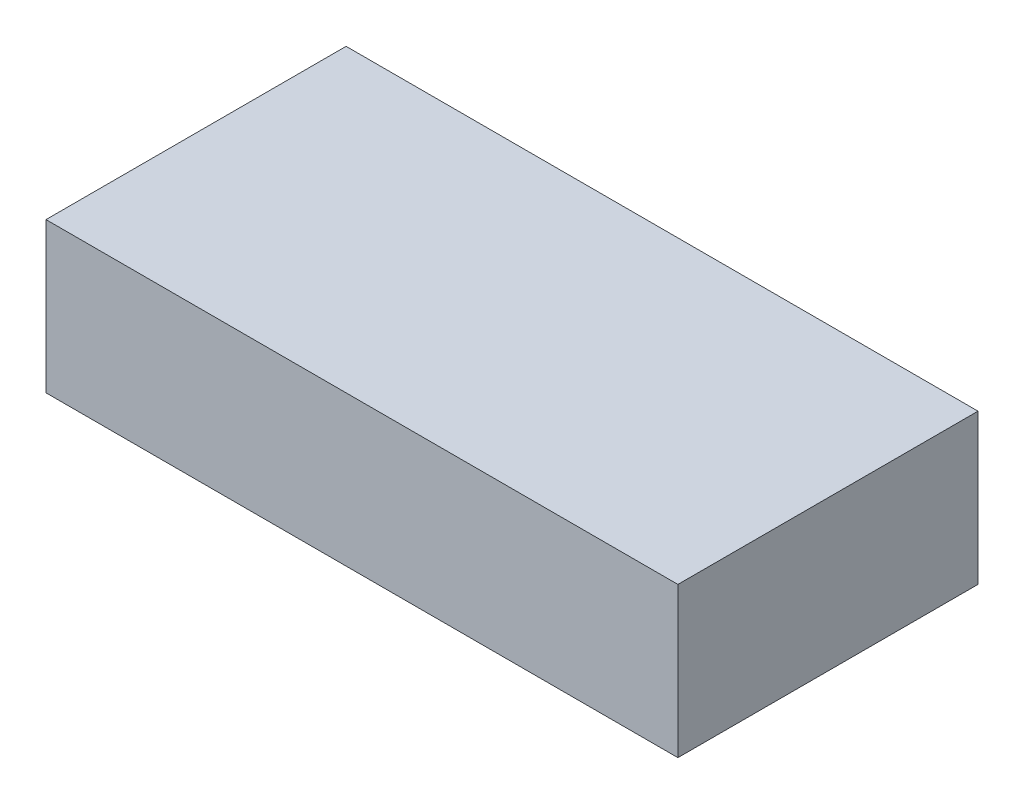
SolidWorks part; units mm, degrees
ref_plane "Front Plane" through (0, 0, 0) normal (0, 0, 1) x (1, 0, 0)
ref_plane "Top Plane" through (0, 0, 0) normal (0, 1, 0) x (1, 0, 0)
ref_plane "Right Plane" through (0, 0, 0) normal (1, 0, 0) x (0, 0, -1)
sketch "Sketch1" plane through (0, 0, 0) normal (0, 1, 0) x (1, 0, 0)
  line L1 (-37.973, -18.034) -> (37.973, -18.034)
  line L2 (-37.973, -18.034) -> (-37.973, 18.034)
  line L3 (-37.973, 18.034) -> (37.973, 18.034)
  line L4 (37.973, -18.034) -> (37.973, 18.034)
  line L5 (-37.973, -18.034) -> (37.973, 18.034) construction
  line L6 (-37.973, 18.034) -> (37.973, -18.034) construction
  point P0 (0, 0)
  dimension "D1" = 75.946
  dimension "D2" = 36.068
extrude "Boss-Extrude1" add sketch "Sketch1" along normal blind 18.034
